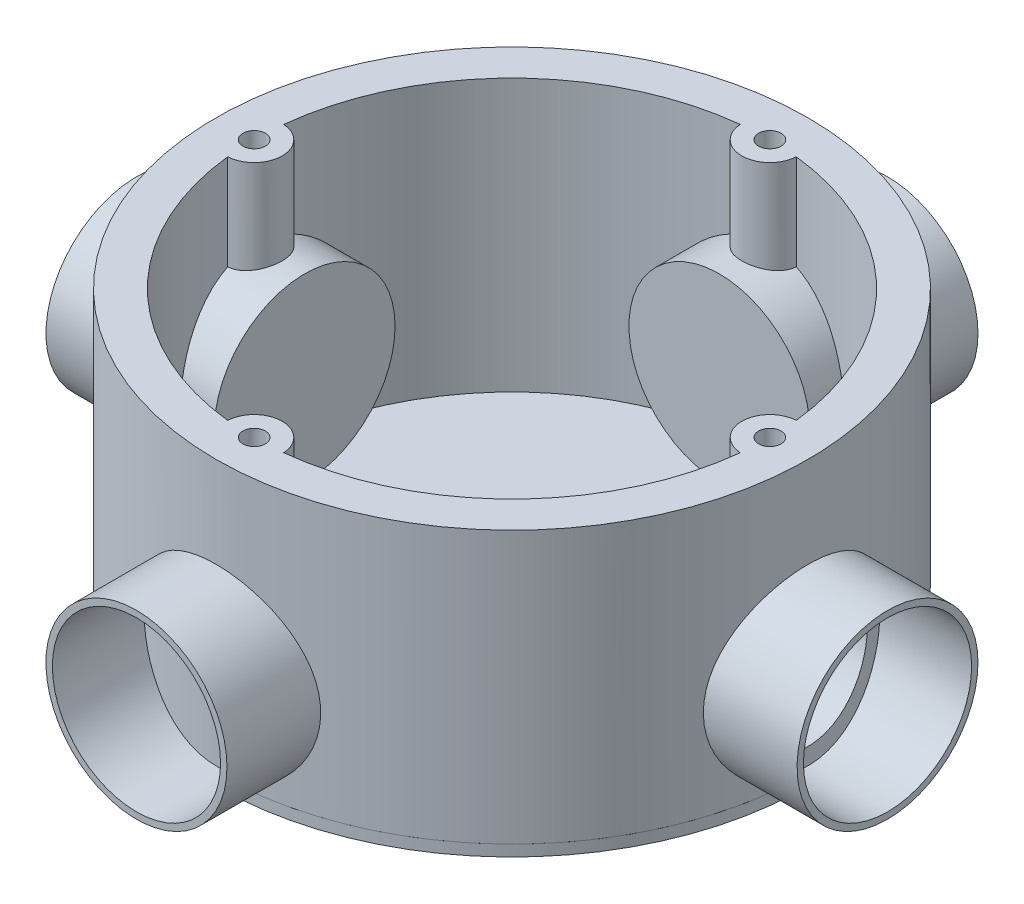
SolidWorks part; units mm, degrees
ref_plane "Plan de face" through (0, 0, 0) normal (0, 0, 1) x (1, 0, 0)
ref_plane "Plan de dessus" through (0, 0, 0) normal (0, 1, 0) x (1, 0, 0)
ref_plane "Plan de droite" through (0, 0, 0) normal (1, 0, 0) x (0, 0, -1)
sketch "Esquisse1" plane through (0, 0, 0) normal (0, 1, 0) x (1, 0, 0)
  line L0 (0, 0) -> (0, 52.8) construction
  line L1 (0, 52.8) -> (0, -52.8) construction
  line L2 (0, -52.8) -> (52.8, 0) construction
  line L3 (52.8, 0) -> (-52.8, 0) construction
  line L4 (0, 46) -> (0, 52.8) construction
  line L5 (0, 46) -> (0, 49.4) construction
  arc A0 (-45.7283, -4.9926) -> (-4.9926, -45.7283) centre (0, 0) ccw
  circle A1 centre (0, 0) radius 52.8
  arc A2 (-4.9926, 45.7283) -> (4.9926, 45.7283) centre (0, 46) ccw
  arc A4 (4.9926, -45.7283) -> (-4.9926, -45.7283) centre (0, -46) ccw
  arc A5 (-45.7283, -4.9926) -> (-45.7283, 4.9926) centre (-46, 0) ccw
  circle A6 centre (46, 0) radius 2
  circle A7 centre (0, -46) radius 2
  circle A8 centre (-46, 0) radius 2
  circle A9 centre (0, 46) radius 2
  arc A10 (4.9926, -45.7283) -> (45.7283, -4.9926) centre (0, 0) ccw
  arc A11 (45.7283, 4.9926) -> (4.9926, 45.7283) centre (0, 0) ccw
  arc A12 (45.7283, 4.9926) -> (45.7283, -4.9926) centre (46, 0) ccw
  arc A13 (-4.9926, 45.7283) -> (-45.7283, 4.9926) centre (0, 0) ccw
extrude "Boss.-Extru.1" add sketch "Esquisse1" along normal blind 48.5
sketch "Esquisse2" plane through (0, 0, 0) normal (0, 0, 1) x (1, 0, 0)
  line L0 (0, 48.5) -> (0, 0) construction
  line L1 (52.8, 48.5) -> (-52.8, 48.5) construction
  line L2 (0, 0) -> (0, 16.15) construction
  line L3 (-44, 48.5) -> (-48, 48.5) construction
  circle A0 centre (0, 16.15) radius 16.15
  circle A1 centre (0, 16.15) radius 15
sketch "Esquisse3" plane through (0, 48.5, 0) normal (0, 1, 0) x (1, 0, 0)
  line L0 (0, -46) -> (0, -37) construction
  line L1 (0, -37) -> (-8.1337, -37) construction
ref_plane "Plan1" through (0, 0, 37) normal (0, 0, 1) x (1, 0, 0)
extrude "Boss.-Extru.2" add sketch "Esquisse2" along normal blind 30 from surface starting at plane "Plan1"
sketch "Esquisse4" plane through (0, 0, 37) normal (0, 0, -1) x (-1, 0, 0)
  circle A0 centre (0, 16.15) radius 16.15
extrude "Boss.-Extru.3" add sketch "Esquisse4" against normal blind 3
sketch "Esquisse5" plane through (0, 48.5, 0) normal (0, 1, 0) x (1, 0, 0)
  line L0 (46, 0) -> (37, 0) construction
  line L1 (0, 46) -> (0, 37) construction
  line L2 (0, 37) -> (-46, 0) construction
  line L3 (-46, 0) -> (-37, 0) construction
ref_plane "Plan2" through (0, 0, -37) normal (0, 0, 1) x (1, 0, 0)
ref_plane "Plan3" through (-37, 0, 0) normal (1, 0, 0) x (0, 0, -1)
ref_plane "Plan4" through (37, 0, 0) normal (1, 0, 0) x (0, 0, -1)
sketch "Esquisse6" plane through (-37, 0, 0) normal (1, 0, 0) x (0, 0, -1)
  line L0 (0, 0) -> (0, 16.14) construction
  circle A0 centre (0, 16.14) radius 16.14
  circle A1 centre (0, 16.14) radius 15
extrude "Boss.-Extru.4" add sketch "Esquisse6" against normal blind 30
sketch "Esquisse7" plane through (-37, 0, 0) normal (1, 0, 0) x (0, 0, -1)
  circle A0 centre (0, 16.14) radius 16.14
extrude "Boss.-Extru.5" add sketch "Esquisse7" against normal blind 3
sketch "Esquisse8" plane through (0, 0, -37) normal (0, 0, 1) x (1, 0, 0)
  line L0 (0, 0) -> (0, 16.14) construction
  circle A0 centre (0, 16.14) radius 16.14
  circle A1 centre (0, 16.14) radius 15
extrude "Boss.-Extru.6" add sketch "Esquisse8" against normal blind 30
sketch "Esquisse9" plane through (0, 0, -37) normal (0, 0, 1) x (1, 0, 0)
  circle A0 centre (0, 16.14) radius 16.14
extrude "Boss.-Extru.7" add sketch "Esquisse9" against normal blind 3
sketch "Esquisse10" plane through (37, 0, 0) normal (1, 0, 0) x (0, 0, -1)
  line L0 (0, 0) -> (0, 16.14) construction
  circle A0 centre (0, 16.14) radius 16.14
  circle A1 centre (0, 16.14) radius 15
extrude "Boss.-Extru.8" add sketch "Esquisse10" along normal blind 30
sketch "Esquisse11" plane through (37, 0, 0) normal (-1, 0, 0) x (0, 0, 1)
  circle A0 centre (0, 16.14) radius 16.14
extrude "Boss.-Extru.9" add sketch "Esquisse11" against normal blind 3
sketch "Esquisse12" plane through (0, 0, 0) normal (0, -1, 0) x (-1, 0, 0)
  circle A0 centre (0, 0) radius 52.8
extrude "Boss.-Extru.12" add sketch "Esquisse12" along normal blind 2 separate body
sketch "Esquisse13" plane through (0, 0, 0) normal (0, 1, 0) x (1, 0, 0)
  line L0 (16.14, 40.0378) -> (16.14, 31.0446) construction
  line L1 (16.14, 37) -> (16.14, 43.0755) construction
  line L2 (16.14, 31.0446) -> (16.14, 37) construction
  line L3 (-27.775, 37) -> (27.775, 37) construction
  line L4 (16.14, 37) -> (37, 16.14) construction
  line L5 (37, -27.775) -> (37, 27.775) construction
  circle A0 centre (26.57, 26.57) radius 6
  circle A1 centre (26.57, 26.57) radius 3.9541
extrude "Boss.-Extru.13" add sketch "Esquisse13" along normal blind 3.8
sketch "Esquisse14" plane through (0, 0, 0) normal (0, 1, 0) x (1, 0, 0)
  line L0 (-40.0378, -16.14) -> (-37, -16.14) construction
  line L1 (-43.0755, -16.14) -> (-37, -16.14) construction
  line L2 (-37, -27.775) -> (-37, 27.775) construction
  line L3 (-37, -16.14) -> (-16.15, -37) construction
  circle A0 centre (-26.575, -26.57) radius 6
  circle A1 centre (-26.575, -26.57) radius 3
extrude "Boss.-Extru.14" add sketch "Esquisse14" along normal blind 3.8
sketch "Esquisse15" plane through (0, 0, 0) normal (0, 1, 0) x (1, 0, 0)
  circle A0 centre (0, 0) radius 7.5
extrude "Boss.-Extru.15" add sketch "Esquisse15" along normal blind 3 contours A0
fillet "Congé1" radius 10 1 edges at (0, 3, 7.5)
sketch "Esquisse16" plane through (40, 0, 0) normal (1, 0, 0) x (0, 0, -1)
  circle A0 centre (0, 16.14) radius 12
extrude "Enlèv. mat.-Extru.1" cut sketch "Esquisse16" against normal blind 10 and the other way blind 30
